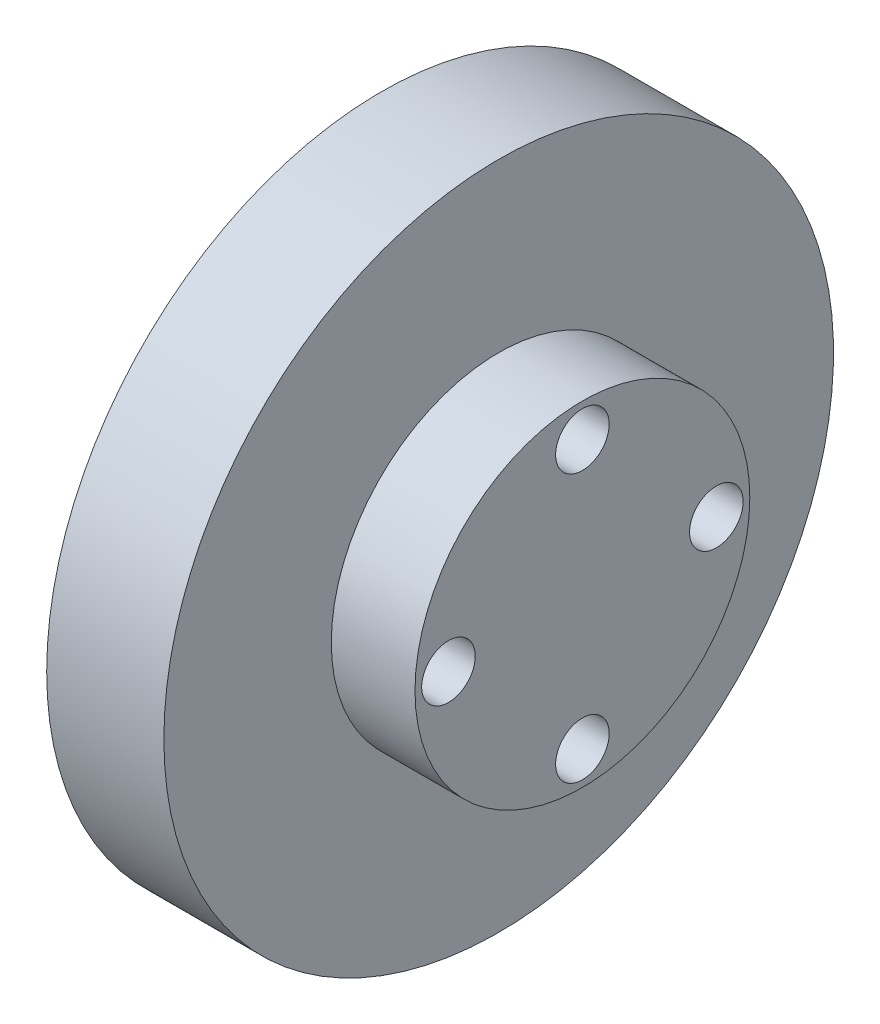
SolidWorks part; units mm, degrees
ref_plane "前视基准面" through (0, 0, 0) normal (0, 0, 1) x (1, 0, 0)
ref_plane "上视基准面" through (0, 0, 0) normal (0, 1, 0) x (1, 0, 0)
ref_plane "右视基准面" through (0, 0, 0) normal (1, 0, 0) x (0, 0, -1)
sketch "草图1" plane through (0, 0, 0) normal (0, 0, 1) x (1, 0, 0)
  line L0 (0, 0) -> (17.2433, 0) construction
  line L1 (0, 0) -> (0, 2)
  line L2 (0, 2) -> (10, 2)
  line L3 (10, 2) -> (10, 20)
  line L4 (10, 20) -> (17, 20)
  line L5 (17, 20) -> (17, 10)
  line L6 (17, 10) -> (22, 10)
  line L7 (22, 10) -> (22, 0)
  line L8 (22, 0) -> (0, 0)
  dimension "D1" = 2
  dimension "D2" = 20
  dimension "D3" = 10
  dimension "D4" = 7
  dimension "D5" = 10
  dimension "D6" = 5
revolve "旋转1" add sketch "草图1" angle 360 about L0
sketch "草图3" plane through (0, 0, 0) normal (0, 0, 1) x (1, 0, 0)
  line L0 (0, 2) -> (0, -2) construction
  line L1 (0, 2.3) -> (10, 2.3)
  line L2 (0, 2.3) -> (0, -2)
  line L3 (0, -2) -> (10, -2)
  line L4 (10, 2.3) -> (10, -2)
  dimension "D1" = 4.3
extrude "切除-拉伸1" cut sketch "草图3" against normal blind 10 and the other way blind 10
sketch "草图4" plane through (22, 0, 0) normal (1, 0, 0) x (0, 0, -1)
  circle A0 centre (0, 8) radius 1.6
  circle A1 centre (8, 0) radius 1.6
  circle A2 centre (0, -8) radius 1.6
  circle A3 centre (-8, 0) radius 1.6
  dimension "D1" = 3.2
  dimension "D2" = 8
  dimension "D3" = 8
  dimension "D4" = 8
  dimension "D5" = 8
extrude "切除-拉伸2" cut sketch "草图4" against normal blind 23
